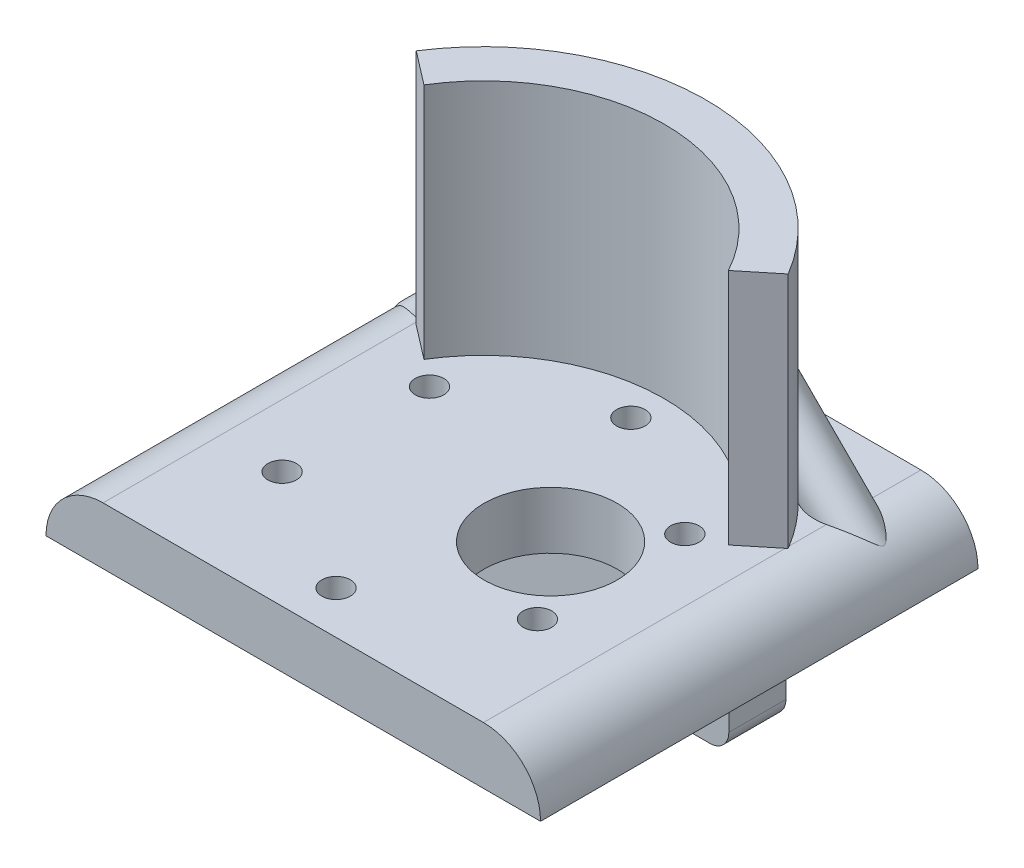
SolidWorks part; units mm, degrees
ref_plane "Front Plane" through (0, 0, 0) normal (0, 0, 1) x (1, 0, 0)
ref_plane "Top Plane" through (0, 0, 0) normal (0, 1, 0) x (1, 0, 0)
ref_plane "Right Plane" through (0, 0, 0) normal (1, 0, 0) x (0, 0, -1)
sketch "Sketch3" plane through (0, 0, 0) normal (0, 0, 1) x (1, 0, 0)
  line L0 (-20, 10.2406) -> (20, 10.2406)
  line L1 (26, 4.2406) -> (26, -13.7594)
  line L2 (20, -19.7594) -> (-20, -19.7594)
  line L3 (0, 19.985) -> (0, -19.985) construction
  line L4 (-26, 4.2406) -> (-26, -13.7594)
  arc A0 (20, 10.2406) -> (26, 4.2406) centre (20, 4.2406) cw
  arc A1 (26, -13.7594) -> (20, -19.7594) centre (20, -13.7594) cw
  arc A2 (-26, -13.7594) -> (-20, -19.7594) centre (-20, -13.7594) ccw
  arc A3 (-20, 10.2406) -> (-26, 4.2406) centre (-20, 4.2406) ccw
  point P12 (0, 0)
  point P14 (0, -19.7594)
  point P19 (0, 10.2406)
  dimension "D3" = 6
  dimension "D4" = 6
  dimension "D1" = 30
  dimension "D2" = 52
extrude "Boss-Extrude1" add sketch "Sketch3" along normal blind 6
sketch "Sketch4" plane through (0, 0, 6) normal (0, 0, 1) x (1, 0, 0)
  line L0 (-26, 4.2406) -> (26, 4.2406)
  line L1 (20, 10.2406) -> (-20, 10.2406)
  arc A0 (26, 4.2406) -> (20, 10.2406) centre (20, 4.2406) ccw
  arc A1 (-20, 10.2406) -> (-26, 4.2406) centre (-20, 4.2406) ccw
extrude "Boss-Extrude2" add sketch "Sketch4" along normal blind 40
sketch "Sketch7" plane through (0, 0, 0) normal (0, 0, -1) x (-1, 0, 0)
  circle A0 centre (0, -4.7594) radius 4
  dimension "D1" = 8
sketch "Sketch9" plane through (0, 10.2406, 0) normal (0, 1, 0) x (1, 0, 0)
  line L0 (20, -46) -> (-20, -46) construction
  circle A0 centre (0, -26) radius 18.5
  circle A1 centre (0, -26) radius 17
  circle A2 centre (0, -10.5) radius 1.5
  circle A3 centre (13.4234, -18.25) radius 1.5
  circle A4 centre (13.4234, -33.75) radius 1.5
  circle A5 centre (0, -41.5) radius 1.5
  circle A6 centre (-13.4234, -33.75) radius 1.5
  circle A7 centre (-13.4234, -18.25) radius 1.5
  point P20 (0, -26)
  dimension "D1" = 37
  dimension "D3" = 34
  dimension "D4" = 3
  dimension "D2" = 20
  dimension "D5" = 6
extrude "Cut-Extrude1" cut sketch "Sketch9" against normal up to next contours A5 | A4 | A6 | A7 | A2 | A3 region at (13.4234, 10.2406, 18.25) region at (0, 10.2406, 10.5) region at (-13.4234, 10.2406, 18.25) region at (-13.4234, 10.2406, 33.75) region at (0, 10.2406, 41.5) region at (13.4234, 10.2406, 33.75)
sketch "Sketch10" plane through (0, 10.2406, 0) normal (0, 1, 0) x (1, 0, 0)
  line L0 (0, 0) -> (0, -49.8421) construction
  circle A1 centre (7.0591, -26) radius 7
  point P0 (0, -26)
  dimension "D1" = 14
extrude "Cut-Extrude2" cut sketch "Sketch10" against normal up to next
sketch "Sketch11" plane through (0, 10.2406, 0) normal (0, 1, 0) x (1, 0, 0)
  line L5 (16.7101, -16.9573) -> (20.1695, -14.1361)
  line L6 (-16.1937, -16.0619) -> (-19.6986, -13.3697)
  arc A3 (-16.1937, -16.0619) -> (16.7101, -16.9573) centre (0, -26) cw
  arc A4 (-19.6986, -13.3697) -> (20.1695, -14.1361) centre (0, -26) cw
  dimension "D1" = 19
  dimension "D2" = 23.4
extrude "Boss-Extrude4" add sketch "Sketch11" along normal blind 25
ref_axis "Axis2" through (26, 10.2406, 0) along (0, 0, 1)
ref_plane "Plane1" through (7.8797, -7.8797, 0) normal (-0.7071, 0.7071, 0) x (0, 0, 1)
ref_axis "Axis3" through (-26, 10.2406, 6) along (0, 0, -1)
ref_plane "Plane2" through (-7.8797, -7.8797, 0) normal (0.7071, 0.7071, 0) x (0, 0, -1)
sketch "Sketch12" plane through (7.8797, -7.8797, 0) normal (-0.7071, 0.7071, 0) x (0, 0, 1)
  circle A0 centre (7.5748, 20.5948) radius 2.5
  dimension "D1" = 5
extrude "Boss-Extrude5" add sketch "Sketch12" along normal up to next
sketch "Sketch14" plane through (-7.8797, -7.8797, 0) normal (0.7071, 0.7071, 0) x (0, 0, -1)
  circle A0 centre (-10.2833, 20.7805) radius 2.5
  dimension "D1" = 5
extrude "Boss-Extrude6" add sketch "Sketch14" along normal up to next
sketch "Sketch15" plane through (0, 0, 0) normal (0, 0, -1) x (-1, 0, 0)
  line L0 (16.0985, 10.2406) -> (-15.6803, 10.2406) construction
  line L1 (-5.7983, -22.9075) -> (-48.6932, -22.9075)
  line L2 (-5.7983, -22.9075) -> (-5.7983, 4.2406)
  line L3 (-5.7983, 4.2406) -> (-48.6932, 4.2406)
  line L4 (-48.6932, -22.9075) -> (-48.6932, 4.2406)
  dimension "D1" = 6
extrude "Cut-Extrude3" cut sketch "Sketch15" against normal up to surface (6 mm away) up to face at (0, -10.1736, 6)
fillet "Fillet1" radius 2 2 edges at (5.7983, -19.7594, 3) (5.7983, 4.2406, 3)
extrude "Cut-Extrude4" cut sketch "Sketch7" against normal blind 3
